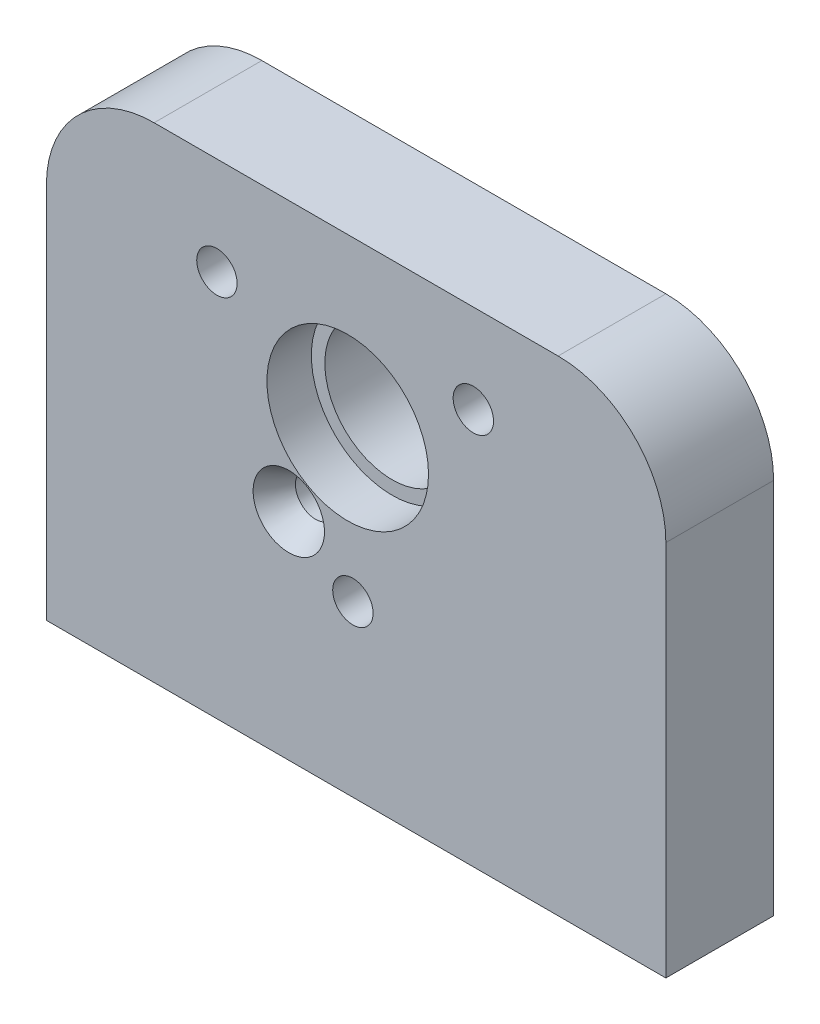
SolidWorks part; units mm, degrees
material "6061 Alloy"
ref_plane "Front Plane" through (0, 0, 0) normal (0, 0, 1) x (1, 0, 0)
ref_plane "Top Plane" through (0, 0, 0) normal (0, 1, 0) x (1, 0, 0)
ref_plane "Right Plane" through (0, 0, 0) normal (1, 0, 0) x (0, 0, -1)
ref_plane "Plane1" through (0, 0, 4.5) normal (0, 0, 1) x (1, 0, 0)
sketch "Sketch1" plane through (0, 0, 4.5) normal (0, 0, 1) x (1, 0, 0)
  line L0 (23, -18) -> (23, 18)
  line L1 (23, 18) -> (-23, 18)
  line L2 (-23, 18) -> (-23, -18)
  line L3 (-23, -18) -> (23, -18)
extrude "Boss-Extrude1" add sketch "Sketch1" against normal blind 8
ref_plane "Plane2" through (0, -2, 0) normal (0, 1, 0) x (1, 0, 0)
hole_wizard "M3x0.5 Tapped Hole2" positions "Sketch6" profile "Sketch5" tap size "M3x0.5" standard "ANSI Metric"
sketch "Sketch6" plane through (0, -18, 0) normal (0, -1, 0) x (-1, 0, 0)
  line L0 (23, -4.5) -> (-23, -4.5) construction
  point P0 (0, -0.5)
  dimension "D1" = 4
sketch "Sketch5" plane through (0, -18, 0.5) normal (1, 0, 0) x (0, 0, -1)
  line L0 (0, 0) -> (0, 8.2511)
  line L1 (0, 8.2511) -> (1.25, 7.5)
  line L2 (1.25, 7.5) -> (1.25, 0)
  line L5 (1.25, 0) -> (0, 0)
  line L10 (0, 8.2511) -> (-1.25, 7.5) construction
  line L11 (0, -6.35) -> (0, 107.95) construction
  dimension "Tap Drill Dia." = 2.5
  dimension "Tap Drill Depth" = 7.5
  dimension "Drill Angle" = 118
hole_wizard "M3x0.5 Tapped Hole1" positions "Sketch8" profile "Sketch7" tap size "M3x0.5" standard "ANSI Metric"
sketch "Sketch8" plane through (0, -18, 0) normal (0, -1, 0) x (-1, 0, 0)
  line L0 (23, -4.5) -> (-23, -4.5) construction
  point P0 (19, -0.5)
  point P1 (-19, -0.5)
  dimension "D1" = 4
sketch "Sketch7" plane through (-19, -18, 0.5) normal (1, 0, 0) x (0, 0, -1)
  line L0 (0, 0) -> (0, 8.2511)
  line L1 (0, 8.2511) -> (1.25, 7.5)
  line L2 (1.25, 7.5) -> (1.25, 0)
  line L5 (1.25, 0) -> (0, 0)
  line L10 (0, 8.2511) -> (-1.25, 7.5) construction
  line L11 (0, -6.35) -> (0, 107.95) construction
  dimension "Tap Drill Dia." = 2.5
  dimension "Tap Drill Depth" = 7.5
  dimension "Drill Angle" = 118
fillet "Fillet2" radius 8 2 edges at (23, 18, 0.5) (-23, 18, 0.5) tangent propagation no
sketch "Sketch16" plane through (0, 0, -3.5) normal (0, 0, -1) x (-1, 0, 0)
  line L0 (23, -18) -> (-23, -18) construction
  line L1 (2.5, -4.5) -> (7.5, -4.5)
  line L2 (2.5, -4.5) -> (2.5, 0.5)
  line L3 (2.5, 0.5) -> (7.5, 0.5)
  line L4 (7.5, -4.5) -> (7.5, 0.5)
  line L5 (2.5, -4.5) -> (7.5, 0.5) construction
  line L6 (2.5, 0.5) -> (7.5, -4.5) construction
  line L9 (23, 10) -> (23, -18) construction
  point P0 (5, -2)
  dimension "D1" = 16
  dimension "D2" = 18
  dimension "D3" = 5
extrude "Cut-Extrude1" cut sketch "Sketch16" against normal blind 4.5
hole_wizard "CSK for M3 SFHCS1" positions "3DSketch1" profile "Sketch17" countersink size "M3" standard "ANSI Metric"
sketch3d "3DSketch1"
  line L0 (-23, -18, 4.5) -> (23, -18, 4.5) construction
  line L1 (-23, 10, 4.5) -> (-23, -18, 4.5) construction
  point P0 (-5, -2, 4.5)
  dimension "D1" = 16
  dimension "D2" = 18
sketch "Sketch17" plane through (-5, -2, 4.5) normal (1, 0, 0) x (0, -1, 0)
  line L0 (0, 0) -> (0, 10.4013)
  line L1 (0, 10.4013) -> (1.5, 9.5)
  line L2 (1.5, 9.5) -> (1.5, 1.9919)
  line L3 (1.5, 1.9919) -> (2.65, 0)
  line L5 (2.65, 0) -> (0, 0)
  line L6 (-1.5, 1.9919) -> (-2.65, 0) construction
  line L10 (0, 10.4013) -> (-1.5, 9.5) construction
  line L11 (0, -6.35) -> (0, 107.95) construction
  dimension "Hole Dia." = 3
  dimension "Hole Depth" = 9.5
  dimension "Near C'Sink Dia." = 5.3
  dimension "Near C'Sink Angle" = 60
  dimension "Drill Angle" = 118
hole_wizard "Hole1" positions "Sketch12" profile "Sketch11" legacy end condition through all
sketch "Sketch12" plane through (0, 0, 4.5) normal (0, 0, 1) x (1, 0, 0)
  line L0 (-5, -2) -> (-0.625, 5.5777) construction
  line L1 (-0.625, 5.5777) -> (-0.625, -18) construction
  line L2 (-23, -18) -> (23, -18) construction
  point P0 (-0.625, 5.5777)
  dimension "D1" = 8.75
  dimension "D2" = 30
sketch "Sketch11" plane through (-0.625, 5.5777, 4.5) normal (1, 0, 0) x (0, -1, 0)
  line L0 (0, 0) -> (0, 8)
  line L1 (0, 8) -> (5, 8)
  line L2 (5, 8) -> (5, 3.3)
  line L3 (5, 3.3) -> (6, 3.3)
  line L4 (6, 3.3) -> (6, 0)
  line L5 (6, 0) -> (0, 0)
  line L6 (0, 110) -> (0, -10) construction
  dimension "Diameter" = 10
  dimension "Depth" = 8
  dimension "C-Bore Diameter" = 12
  dimension "C-Bore Depth" = 3.3
hole_wizard "CSK for M3 SFHCS2" positions "Sketch10" profile "Sketch9" countersink size "M3" standard "ANSI Metric"
sketch "Sketch10" plane through (0, 0, -3.5) normal (0, 0, -1) x (-1, 0, 0)
  line L1 (10.3374, 10.7419) -> (-8.7035, 11.4068) construction
  line L2 (-8.7035, 11.4068) -> (0.2411, -5.4156) construction
  line L3 (0.2411, -5.4156) -> (10.3374, 10.7419) construction
  line L4 (0.625, 5.5777) -> (0.2411, -5.4156) construction
  line L7 (0.625, 5.5777) -> (0.625, -18) construction
  line L8 (23, -18) -> (-23, -18) construction
  circle A0 centre (0.625, 5.5777) radius 5.5 construction
  point P30 (-8.7035, 11.4068)
  point P33 (10.3374, 10.7419)
  point P36 (0.2411, -5.4156)
  dimension "D1" = 2
sketch "Sketch9" plane through (8.7035, 11.4068, -3.5) normal (1, 0, 0) x (0, 1, 0)
  line L0 (0, 0) -> (0, 10.4013)
  line L1 (0, 10.4013) -> (1.5, 9.5)
  line L2 (1.5, 9.5) -> (1.5, 2.0785)
  line L3 (1.5, 2.0785) -> (2.7, 0)
  line L5 (2.7, 0) -> (0, 0)
  line L6 (-1.5, 2.0785) -> (-2.7, 0) construction
  line L10 (0, 10.4013) -> (-1.5, 9.5) construction
  line L11 (0, -6.35) -> (0, 107.95) construction
  dimension "Hole Dia." = 3
  dimension "Hole Depth" = 9.5
  dimension "Near C'Sink Dia." = 5.4
  dimension "Near C'Sink Angle" = 60
  dimension "Drill Angle" = 118
fillet "Fillet3" radius 1 4 edges at (-2.5, -4.5, -1.0226) (-7.5, -4.5, -1.25) (-7.5, 0.5, -1.25) (-2.5, 0.5, -1.25)
sketch "Sketch18" plane through (0, 0, -3.5) normal (0, 0, -1) x (-1, 0, 0)
  line L0 (0.625, 18) -> (0.625, -18) construction
  line L1 (6.125, 15.104) -> (-10.375, 5.5777) construction
  line L2 (-10.375, 5.5777) -> (6.125, -3.9486) construction
  line L3 (6.125, -3.9486) -> (6.125, 15.104) construction
  line L4 (-15, 18) -> (15, 18) construction
  line L5 (23, -18) -> (-23, -18) construction
  line L6 (0.625, 5.5777) -> (6.125, -3.9486) construction
  circle A0 centre (0.625, 5.5777) radius 5.5 construction
  dimension "D1" = 11
  dimension "D2" = 30
